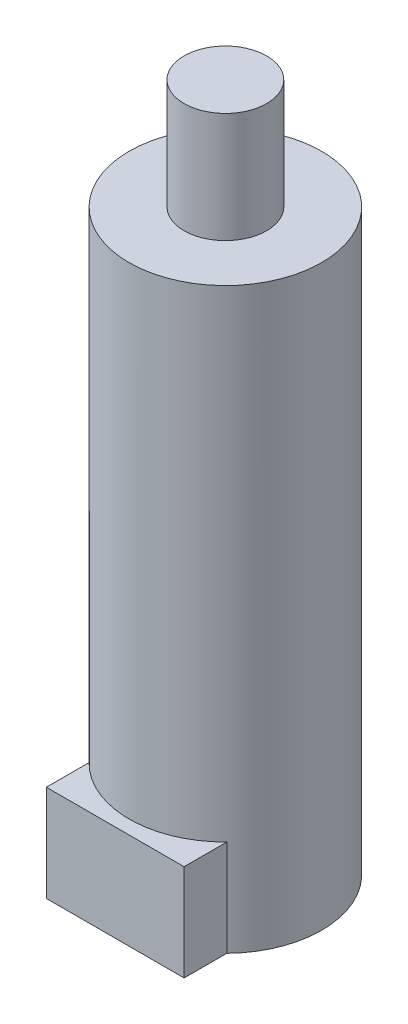
SolidWorks part; units mm, degrees
ref_plane "Front Plane" through (0, 0, 0) normal (0, 0, 1) x (1, 0, 0)
ref_plane "Top Plane" through (0, 0, 0) normal (0, 1, 0) x (1, 0, 0)
ref_plane "Right Plane" through (0, 0, 0) normal (1, 0, 0) x (0, 0, -1)
sketch "Sketch1" plane through (0, 0, 0) normal (0, 1, 0) x (1, 0, 0)
  circle A0 centre (0, 0) radius 11.1125
  dimension "D1" = 22.225
extrude "Boss-Extrude1" add sketch "Sketch1" along normal blind 66.675
sketch "Sketch2" plane through (0, 0, 0) normal (0, 0, 1) x (1, 0, 0)
  line L5 (-11.1125, 0) -> (11.1125, 0) construction
  line L6 (-7.9375, 0) -> (7.9375, 0)
  line L7 (-7.9375, 0) -> (-7.9375, 11.1125)
  line L8 (-7.9375, 11.1125) -> (7.9375, 11.1125)
  line L9 (7.9375, 0) -> (7.9375, 11.1125)
  point P7 (0, 11.1125)
  dimension "D1" = 11.1125
  dimension "D2" = 15.875
extrude "Boss-Extrude2" add sketch "Sketch2" along normal blind 12.7
sketch "Sketch3" plane through (0, 66.675, 0) normal (0, 1, 0) x (1, 0, 0)
  circle A0 centre (0, 0) radius 4.7625
  dimension "D1" = 9.525
extrude "Boss-Extrude3" add sketch "Sketch3" along normal blind 12.7
